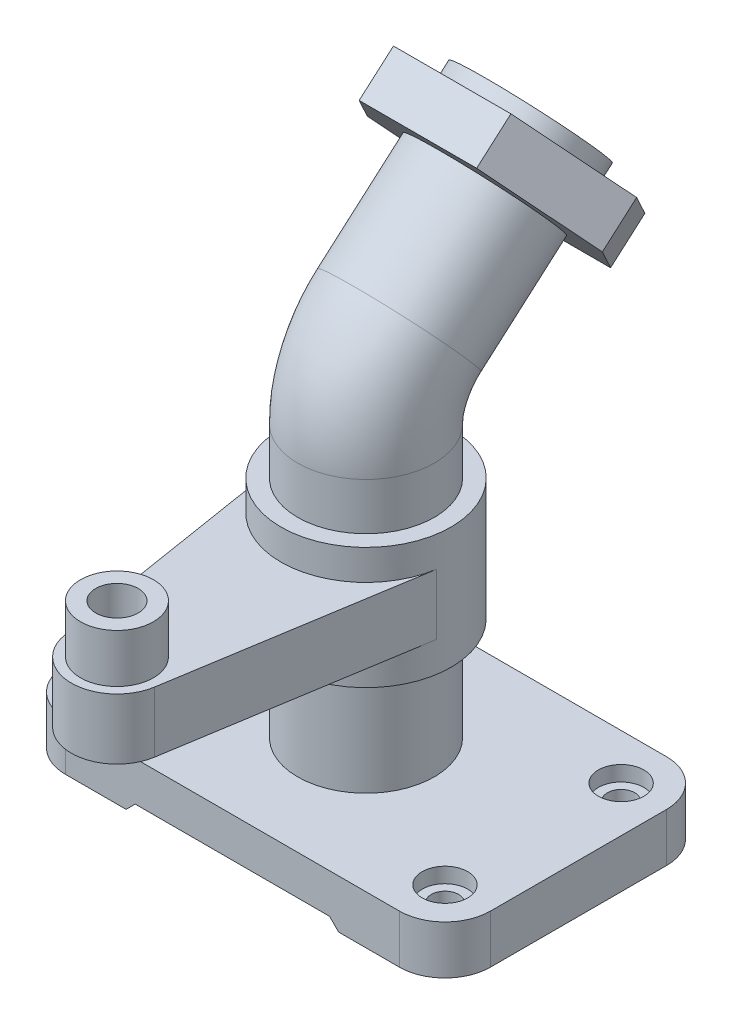
SolidWorks part; units mm, degrees
ref_plane "Front Plane" through (0, 0, 0) normal (0, 0, 1) x (1, 0, 0)
ref_plane "Top Plane" through (0, 0, 0) normal (0, 1, 0) x (1, 0, 0)
ref_plane "Right Plane" through (0, 0, 0) normal (1, 0, 0) x (0, 0, -1)
sketch "Sketch1" plane through (0, 0, 0) normal (0, 1, 0) x (1, 0, 0)
  line L1 (-70, 44) -> (70, 44)
  line L2 (-70, 44) -> (-70, -44)
  line L3 (-70, -44) -> (70, -44)
  line L4 (70, 44) -> (70, -44)
  line L5 (-70, 44) -> (70, -44) construction
  line L6 (-70, -44) -> (70, 44) construction
  point P0 (0, 0)
  dimension "D1" = 140
  dimension "D2" = 88
extrude "Boss-Extrude1" add sketch "Sketch1" along normal blind 16
fillet "Fillet1" radius 15 4 edges at (-70, 8, -44) (70, 8, -44) (-70, 8, 44) (70, 8, 44)
sketch "Sketch4" plane through (0, 16, 0) normal (0, 1, 0) x (1, 0, 0)
  point P0 (-55, 29)
  point P3 (55, 29)
  point P6 (-55, -29)
  point P9 (55, -29)
hole_wizard "Hole2" positions "Sketch4" profile "Sketch2" legacy end condition through all
sketch "Sketch2" plane through (-55, 16, -29) normal (1, 0, 0) x (0, 0, 1)
  line L0 (0, 0) -> (0, 16)
  line L1 (0, 16) -> (4.5, 16)
  line L2 (4.5, 16) -> (4.5, 5)
  line L3 (4.5, 5) -> (7.5, 5)
  line L4 (7.5, 5) -> (7.5, 0)
  line L5 (7.5, 0) -> (0, 0)
  line L6 (0, 110) -> (0, -10) construction
  dimension "Diameter" = 9
  dimension "Depth" = 16
  dimension "C-Bore Diameter" = 15
  dimension "C-Bore Depth" = 5
sketch "Sketch6" plane through (0, 0, 0) normal (1, 0, 0) x (0, 0, -1)
  line L0 (0, 0) -> (0, 105.476)
  line L1 (10.9321, 129.5622) -> (54.1939, 167.4027)
  arc A0 (0, 105.476) -> (10.9321, 129.5622) centre (32, 105.476) cw
  point P6 (0, 120)
  point P7 (0, 0)
  dimension "D3" = 32
  dimension "D1" = 120
  dimension "D2" = 72
sweep "Sweep1" add path "Sketch6" circular profile diameter 45 parameters "D3"=45
sweep "Cut-Sweep1" cut path "Sketch6<5>" circular profile diameter 12 parameters "D3"=12
sketch "Sketch6<5>" plane through (0, 0, 0) normal (1, 0, 0) x (0, 0, -1) same geometry as "Sketch6"
sketch "Sketch21" plane through (0, 0, 0) normal (0, 1, 0) x (1, 0, 0)
  circle A0 centre (0, 0) radius 28
  dimension "D1" = 56
extrude "Boss-Extrude2" add sketch "Sketch21" along normal blind 40 from offset 50
ref_plane "Plane1" through (0, 70, 0) normal (0, 1, 0) x (1, 0, 0)
sketch "Sketch23" plane through (0, 70, 0) normal (0, 1, 0) x (1, 0, 0)
  line L0 (0, -82) -> (0, 0) construction
  line L1 (-27.6459, -4.439) -> (-14.8103, -84.378)
  line L2 (27.6459, -4.439) -> (14.8103, -84.378)
  arc A0 (-14.8103, -84.378) -> (14.8103, -84.378) centre (0, -82) ccw
  circle A1 centre (0, 0) radius 28 construction
  arc A2 (27.6459, -4.439) -> (-27.6459, -4.439) centre (0, 0) ccw
  dimension "D1" = 30
  dimension "D2" = 82
extrude "Boss-Extrude3" add sketch "Sketch23" along normal mid plane 20
sketch "Sketch25" plane through (0, 70, 0) normal (0, 1, 0) x (1, 0, 0)
  line L0 (-27.6459, -4.439) -> (-14.8103, -84.378) construction
  line L1 (14.8103, -84.378) -> (27.6459, -4.439) construction
  line L2 (-27.6459, -4.439) -> (-14.8103, -84.378)
  line L3 (14.8103, -84.378) -> (27.6459, -4.439)
  line L4 (10.8609, -83.7439) -> (23.6965, -3.8049)
  line L5 (-23.6965, -3.8049) -> (-10.8609, -83.7439)
  circle A0 centre (0, 0) radius 28 construction
  arc A1 (-14.8103, -84.378) -> (14.8103, -84.378) centre (0, -82) ccw construction
  arc A2 (27.6459, -4.439) -> (-27.6459, -4.439) centre (0, 0) ccw
  arc A3 (-14.8103, -84.378) -> (14.8103, -84.378) centre (0, -82) ccw
  arc A4 (23.6965, -3.8049) -> (-23.6965, -3.8049) centre (0, 0) ccw
  arc A5 (-10.8609, -83.7439) -> (10.8609, -83.7439) centre (0, -82) ccw
  dimension "D1" = 4
extrude "Cut-Extrude1" cut sketch "Sketch25" against normal mid plane 12 contours L4 A4 L5 A5
sketch "Sketch27" plane through (0, 80, 0) normal (0, 1, 0) x (1, 0, 0)
  circle A0 centre (0, -82) radius 12
  dimension "D1" = 24
extrude "Boss-Extrude4" add sketch "Sketch27" along normal blind 16
sketch "Sketch28" plane through (0, 96, 0) normal (0, 1, 0) x (1, 0, 0)
  circle A0 centre (0, -82) radius 7
  dimension "D1" = 14
extrude "Cut-Extrude2" cut sketch "Sketch28" against normal up to next
sketch "Sketch30" plane through (0, 0, 0) normal (1, 0, 0) x (0, 0, -1)
  line L0 (0, 0) -> (18.5, 0)
  line L1 (-29, 0) -> (29, 0) construction
  line L2 (18.5, 0) -> (18.5, 54)
  line L3 (18.5, 54) -> (24, 54)
  line L4 (24, 54) -> (24, 86)
  line L5 (24, 86) -> (0, 86)
  line L6 (0, 0) -> (0, 105.476) construction
  line L7 (0, 86) -> (0, 0)
  point P5 (12, 86)
  dimension "D1" = 18.5
  dimension "D2" = 54
  dimension "D3" = 32
  dimension "D4" = 24
revolve "Cut-Revolve1" cut sketch "Sketch30" angle 360 about L7
sweep "Cut-Sweep2" cut path "Sketch6<6>" circular profile diameter 12 parameters "D3"=12
sketch "Sketch6<6>" plane through (0, 0, 0) normal (1, 0, 0) x (0, 0, -1) same geometry as "Sketch6"
sketch "Sketch41" plane through (0, 99.4171, -113.6601) normal (0, 0.6584, -0.7527) x (-1, 0, 0)
  line L1 (19.3412, 56.8232) -> (38.6825, 90.3232)
  line L2 (38.6825, 90.3232) -> (19.3412, 123.8232)
  line L3 (19.3412, 123.8232) -> (-19.3412, 123.8232)
  line L4 (-19.3412, 123.8232) -> (-38.6825, 90.3232)
  line L5 (-38.6825, 90.3232) -> (-19.3412, 56.8232)
  line L6 (-19.3412, 56.8232) -> (19.3412, 56.8232)
  circle A0 centre (0, 90.3232) radius 33.5 construction
  point P1 (0, 0)
  point P10 (0, 123.8232)
  dimension "D1" = 67
extrude "Boss-Extrude5" add sketch "Sketch41" against normal blind 15 from offset 5 offset against normal yes
sketch "Sketch43" plane through (0, 0, 0) normal (1, 0, 0) x (0, 0, -1)
  line L0 (10.9321, 129.5622) -> (54.1939, 167.4027) construction
  line L1 (10.9321, 129.5622) -> (54.1939, 167.4027)
  line L2 (0, 120) -> (22.9928, 93.7131) construction
  line L3 (0, 120) -> (33.7544, 112.3162) construction
  arc A0 (10.9321, 129.5622) -> (0, 105.476) centre (32, 105.476) ccw construction
  arc A1 (10.9321, 129.5622) -> (3.1337, 119.2867) centre (32, 105.476) ccw
  dimension "D1" = 36
sweep "Cut-Sweep3" cut path "Sketch43" circular profile diameter 30 parameters "D3"=30
sketch "Sketch57" plane through (0, 99.4171, -113.6601) normal (0, 0.6584, -0.7527) x (-1, 0, 0)
  circle A0 centre (0, 90.3232) radius 17.5
  dimension "D1" = 35
extrude "Cut-Extrude3" cut sketch "Sketch57" against normal blind 56.4
sketch "Sketch59" plane through (0, 0, 0) normal (0, 0, 1) x (1, 0, 0)
  line L0 (-35, 0) -> (35, 0)
  line L1 (-55, 0) -> (55, 0) construction
  line L2 (35, 0) -> (32, 3)
  line L3 (32, 3) -> (-32, 3)
  line L4 (-32, 3) -> (-35, 0)
  point P4 (0, 0)
  dimension "D1" = 70
  dimension "D2" = 45
  dimension "D3" = 45
  dimension "D4" = 3
extrude "Cut-Extrude4" cut sketch "Sketch59" against normal through all both and the other way through all
